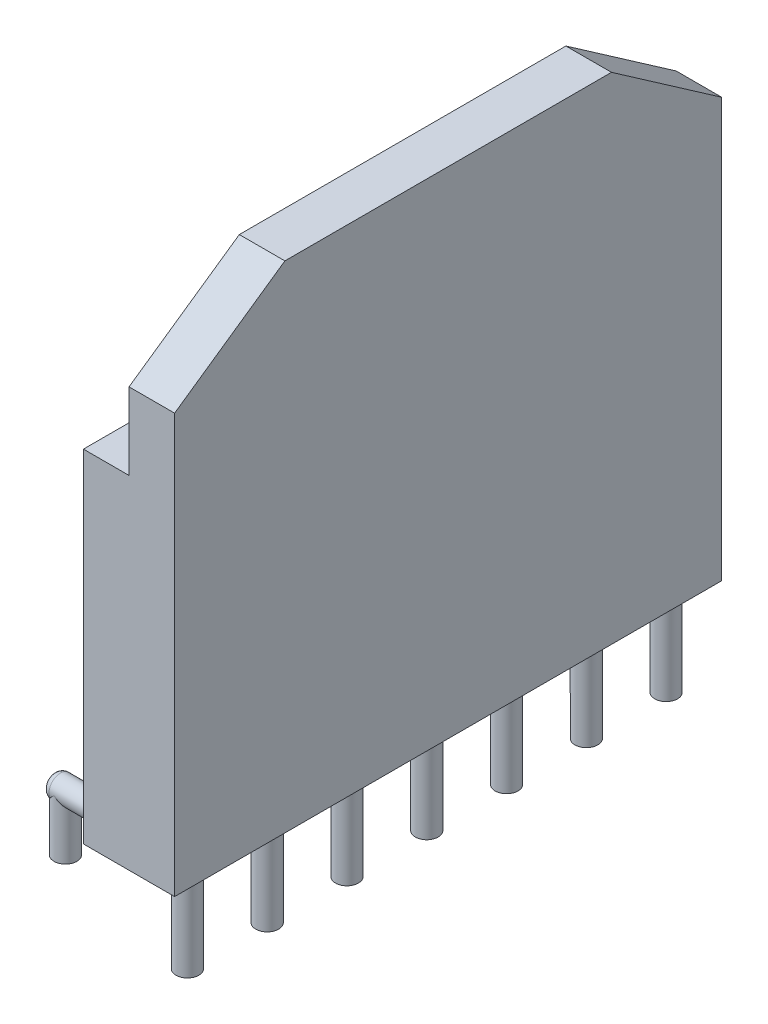
SolidWorks part; units mm, degrees
ref_plane "前视基准面" through (0, 0, 0) normal (0, 0, 1) x (1, 0, 0)
ref_plane "上视基准面" through (0, 0, 0) normal (0, 1, 0) x (1, 0, 0)
ref_plane "右视基准面" through (0, 0, 0) normal (1, 0, 0) x (0, 0, -1)
sketch "草图1" plane through (0, 0, 0) normal (1, 0, 0) x (0, 0, -1)
  line L1 (0, 0) -> (24, 0)
  line L2 (0, 0) -> (0, -15)
  line L3 (0, -15) -> (24, -15)
  line L4 (24, 0) -> (24, -15)
  dimension "D1" = 24
  dimension "D2" = 15
extrude "凸台-拉伸1" add sketch "草图1" along normal blind 4
sketch "草图2" plane through (4, 0, 0) normal (1, 0, 0) x (0, 0, -1)
  line L0 (4.8371, 6.732) -> (0, 3.366)
  line L1 (0, 0) -> (24, 0)
  line L2 (0, 0) -> (0, 3.366)
  line L3 (4.8371, 6.732) -> (19.1629, 6.732)
  line L4 (24, 0) -> (24, 3.366)
  line L5 (19.1629, 6.732) -> (24, 3.366)
  line L6 (12, 9.6947) -> (12, -2.306) construction
extrude "凸台-拉伸2" add sketch "草图2" against normal blind 2
sketch "草图3" plane through (0, -15, 0) normal (0, -1, 0) x (1, 0, 0)
  line L0 (2, 0.9338) -> (2, -25.7103) construction
  circle A0 centre (3.0192, -1.5413) radius 0.5
extrude "凸台-拉伸3" add sketch "草图3" along normal blind 4
pattern_linear "阵列(线性)1" count 7 spacing 3.5 along (0, 0, -1) of "凸台-拉伸3"
sketch "草图4" plane through (0, -15, 0) normal (0, -1, 0) x (1, 0, 0)
  circle A0 centre (1.0293, -3.1914) radius 0.5
extrude "凸台-拉伸4" add sketch "草图4" along normal blind 1.5
sketch "草图5" plane through (0, 0, 0) normal (-1, 0, 0) x (0, 0, 1)
  line L0 (-3.6914, -16.5) -> (-2.6914, -16.5) construction
  circle A0 centre (-3.1914, -16.5) radius 0.5
extrude "凸台-拉伸5" add sketch "草图5" along normal mid plane 3
fillet "圆角2" radius 0.3 1 edges at (1.5, -17, -3.1914)
sketch "草图6" plane through (-1.5, 0, 0) normal (-1, 0, 0) x (0, 0, 1)
  circle A0 centre (-3.1914, -16.5) radius 0.5
extrude "凸台-拉伸6" add sketch "草图6" along normal blind 3
sketch "草图8" plane through (0, -19, 0) normal (0, -1, 0) x (1, 0, 0)
  circle A0 centre (-3.9805, -3.1914) radius 0.5
extrude "凸台-拉伸7" add sketch "草图8" against normal blind 2.5
fillet "圆角3" radius 0.3 1 edges at (-4.5, -16.5, -2.6914)
pattern_linear "阵列(线性)2" count 6 spacing 3.5 along (0, 0, -1) of "凸台-拉伸5", "凸台-拉伸7", "圆角3", "圆角2", "凸台-拉伸4", "凸台-拉伸6"
